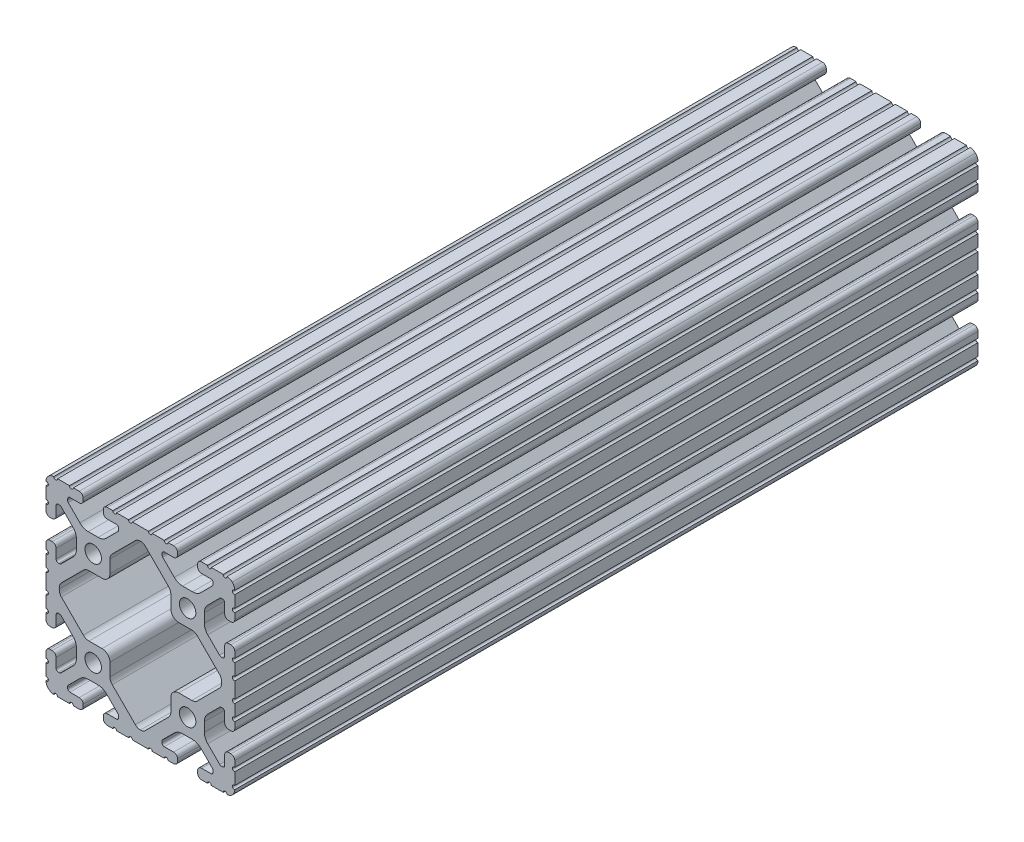
SolidWorks part; units mm, degrees
ref_plane "Front Plane" through (0, 0, 0) normal (0, 0, 1) x (1, 0, 0)
ref_plane "Top Plane" through (0, 0, 0) normal (0, 1, 0) x (1, 0, 0)
ref_plane "Right Plane" through (0, 0, 0) normal (1, 0, 0) x (0, 0, -1)
sketch "Sketch1" plane through (0, 0, 0) normal (0, 0, 1) x (1, 0, 0)
  line L0 (0, 38.1) -> (0, -38.1) construction
  line L1 (-38.1, -38.1) -> (38.1, -38.1) construction
  line L2 (-38.1, -38.1) -> (-38.1, 38.1) construction
  line L3 (-38.1, 38.1) -> (38.1, 38.1) construction
  line L4 (38.1, -38.1) -> (38.1, 38.1) construction
  line L5 (0, 38.1) -> (0, -38.1) construction
  line L6 (-38.1, 0) -> (38.1, 0) construction
  line L7 (-19.05, 19.05) -> (19.05, 19.05) construction
  line L8 (-19.05, 19.05) -> (-19.05, -19.05) construction
  line L9 (-19.05, -19.05) -> (19.05, -19.05) construction
  line L10 (19.05, 19.05) -> (19.05, -19.05) construction
  line L11 (-23.114, 38.1) -> (-23.114, -38.1) construction
  line L12 (-23.114, -38.1) -> (-14.986, 38.1) construction
  line L13 (-14.986, 38.1) -> (-14.986, -38.1) construction
  circle A0 centre (19.05, 19.05) radius 3.3274
  point P0 (0, 0)
  point P9 (0, 0)
  point P12 (-19.05, 0)
  line B0 (-11.3637, -22.8433) -> (-2.0515, -32.1555)
  line B1 (-12.2936, -15.4686) -> (-12.2936, -20.5983)
  line B2 (-20.769, -12.2936) -> (-15.4686, -12.2936)
  line B3 (-31.9021, -2.4756) -> (-23.0141, -11.3637)
  line B4 (-23.0141, 11.3637) -> (-31.9021, 2.4756)
  line B5 (-15.4686, 12.2936) -> (-20.769, 12.2936)
  line B6 (-12.2936, 20.5983) -> (-12.2936, 15.4686)
  line B7 (-2.0515, 32.1555) -> (-11.3637, 22.8433)
  line B8 (11.3637, 22.8433) -> (2.0515, 32.1555)
  line B9 (12.2936, 15.4686) -> (12.2936, 20.5983)
  line B10 (20.769, 12.2936) -> (15.4686, 12.2936)
  line B11 (31.9021, 2.4756) -> (23.0141, 11.3637)
  line B12 (23.0141, -11.3637) -> (31.9021, -2.4756)
  line B13 (15.4686, -12.2936) -> (20.769, -12.2936)
  line B14 (12.2936, -20.5983) -> (12.2936, -15.4686)
  line B15 (2.0515, -32.1555) -> (11.3637, -22.8433)
  line B16 (-4.7773, 38.1) -> (-9.6053, 38.1)
  line B17 (-11.1289, 38.1) -> (-13.4112, 38.1)
  line B18 (-14.986, 36.5252) -> (-14.986, 35.6108)
  line B19 (-13.4112, 34.036) -> (-9.652, 34.036)
  line B20 (-8.763, 33.147) -> (-8.763, 32.4935)
  line B21 (-9.0234, 31.8649) -> (-13.6907, 27.1976)
  line B22 (-17.0493, 25.8064) -> (-21.0507, 25.8064)
  line B23 (-24.4093, 27.1976) -> (-29.1002, 31.8885)
  line B24 (-29.337, 32.7207) -> (-29.337, 33.147)
  line B25 (-28.448, 34.036) -> (-24.6888, 34.036)
  line B26 (-23.114, 35.6108) -> (-23.114, 36.5252)
  line B27 (-24.6888, 38.1) -> (-27.0772, 38.1)
  line B28 (-28.6011, 38.1) -> (-33.4288, 38.1)
  line B29 (-38.1, 33.373) -> (-38.1, 28.5453)
  line B30 (-38.1, 27.0238) -> (-38.1, 24.6302)
  line B31 (-36.5252, 23.0554) -> (-35.6108, 23.0554)
  line B32 (-34.036, 24.6302) -> (-34.036, 28.448)
  line B33 (-33.147, 29.337) -> (-32.6643, 29.337)
  line B34 (-32.0357, 29.0766) -> (-27.1976, 24.2385)
  line B35 (-25.8064, 20.8799) -> (-25.8064, 17.2201)
  line B36 (-27.1976, 13.8615) -> (-31.9489, 9.1101)
  line B37 (-32.7869, 8.763) -> (-33.0603, 8.763)
  line B38 (-34.036, 9.7387) -> (-34.036, 13.4698)
  line B39 (-35.6108, 15.0446) -> (-36.5252, 15.0446)
  line B40 (-38.1, 13.4698) -> (-38.1, 11.075)
  line B41 (-38.1, 9.552) -> (-38.1, 4.7238)
  line B42 (-38.1, 3.2007) -> (-38.1, -3.2007)
  line B43 (-38.1, -4.7238) -> (-38.1, -9.552)
  line B44 (-38.1, -11.075) -> (-38.1, -13.4698)
  line B45 (-36.5252, -15.0446) -> (-35.6108, -15.0446)
  line B46 (-34.036, -13.4698) -> (-34.036, -9.7387)
  line B47 (-33.0603, -8.763) -> (-32.7869, -8.763)
  line B48 (-31.9489, -9.1101) -> (-27.1976, -13.8615)
  line B49 (-25.8064, -17.2201) -> (-25.8064, -20.8799)
  line B50 (-27.1976, -24.2385) -> (-32.0357, -29.0766)
  line B51 (-32.6643, -29.337) -> (-33.147, -29.337)
  line B52 (-34.036, -28.448) -> (-34.036, -24.6302)
  line B53 (-35.6108, -23.0554) -> (-36.5252, -23.0554)
  line B54 (-38.1, -24.6302) -> (-38.1, -27.0238)
  line B55 (-38.1, -28.5453) -> (-38.1, -33.373)
  line B56 (-33.4288, -38.1) -> (-28.6011, -38.1)
  line B57 (-27.0772, -38.1) -> (-24.6888, -38.1)
  line B58 (-23.114, -36.5252) -> (-23.114, -35.6108)
  line B59 (-24.6888, -34.036) -> (-28.448, -34.036)
  line B60 (-29.337, -33.147) -> (-29.337, -32.7207)
  line B61 (-29.1002, -31.8885) -> (-24.4093, -27.1976)
  line B62 (-21.0507, -25.8064) -> (-17.0493, -25.8064)
  line B63 (-13.6907, -27.1976) -> (-9.0234, -31.8649)
  line B64 (-8.763, -32.4935) -> (-8.763, -33.147)
  line B65 (-9.652, -34.036) -> (-13.4112, -34.036)
  line B66 (-14.986, -35.6108) -> (-14.986, -36.5252)
  line B67 (-13.4112, -38.1) -> (-11.1289, -38.1)
  line B68 (-9.6053, -38.1) -> (-4.7773, -38.1)
  line B69 (-3.2537, -38.1) -> (3.2537, -38.1)
  line B70 (4.7773, -38.1) -> (9.6053, -38.1)
  line B71 (11.1289, -38.1) -> (13.4112, -38.1)
  line B72 (14.986, -36.5252) -> (14.986, -35.6108)
  line B73 (13.4112, -34.036) -> (9.652, -34.036)
  line B74 (8.763, -33.147) -> (8.763, -32.4935)
  line B75 (9.0234, -31.8649) -> (13.6907, -27.1976)
  line B76 (17.0493, -25.8064) -> (21.0507, -25.8064)
  line B77 (24.4093, -27.1976) -> (29.1002, -31.8885)
  line B78 (29.337, -32.7207) -> (29.337, -33.147)
  line B79 (28.448, -34.036) -> (24.6888, -34.036)
  line B80 (23.114, -35.6108) -> (23.114, -36.5252)
  line B81 (24.6888, -38.1) -> (27.0772, -38.1)
  line B82 (28.6011, -38.1) -> (33.4288, -38.1)
  line B83 (38.1, -33.373) -> (38.1, -28.5453)
  line B84 (38.1, -27.0238) -> (38.1, -24.6302)
  line B85 (36.5252, -23.0554) -> (35.6108, -23.0554)
  line B86 (34.036, -24.6302) -> (34.036, -28.448)
  line B87 (33.147, -29.337) -> (32.6643, -29.337)
  line B88 (32.0357, -29.0766) -> (27.1976, -24.2385)
  line B89 (25.8064, -20.8799) -> (25.8064, -17.2201)
  line B90 (27.1976, -13.8615) -> (31.9489, -9.1101)
  line B91 (32.7869, -8.763) -> (33.0603, -8.763)
  line B92 (34.036, -9.7387) -> (34.036, -13.4698)
  line B93 (35.6108, -15.0446) -> (36.5252, -15.0446)
  line B94 (38.1, -13.4698) -> (38.1, -11.075)
  line B95 (38.1, -9.552) -> (38.1, -4.7238)
  line B96 (38.1, -3.2007) -> (38.1, 3.2007)
  line B97 (38.1, 4.7238) -> (38.1, 9.552)
  line B98 (38.1, 11.075) -> (38.1, 13.4698)
  line B99 (36.5252, 15.0446) -> (35.6108, 15.0446)
  line B100 (34.036, 13.4698) -> (34.036, 9.7387)
  line B101 (33.0603, 8.763) -> (32.7869, 8.763)
  line B102 (31.9489, 9.1101) -> (27.1976, 13.8615)
  line B103 (25.8064, 17.2201) -> (25.8064, 20.8799)
  line B104 (27.1976, 24.2385) -> (32.0357, 29.0766)
  line B105 (32.6643, 29.337) -> (33.147, 29.337)
  line B106 (34.036, 28.448) -> (34.036, 24.6302)
  line B107 (35.6108, 23.0554) -> (36.5252, 23.0554)
  line B108 (38.1, 24.6302) -> (38.1, 27.0238)
  line B109 (38.1, 28.5453) -> (38.1, 33.373)
  line B110 (33.4288, 38.1) -> (28.6011, 38.1)
  line B111 (27.0772, 38.1) -> (24.6888, 38.1)
  line B112 (23.114, 36.5252) -> (23.114, 35.6108)
  line B113 (24.6888, 34.036) -> (28.448, 34.036)
  line B114 (29.337, 33.147) -> (29.337, 32.7207)
  line B115 (29.1002, 31.8885) -> (24.4093, 27.1976)
  line B116 (21.0507, 25.8064) -> (17.0493, 25.8064)
  line B117 (13.6907, 27.1976) -> (9.0234, 31.8649)
  line B118 (8.763, 32.4935) -> (8.763, 33.147)
  line B119 (9.652, 34.036) -> (13.4112, 34.036)
  line B120 (14.986, 35.6108) -> (14.986, 36.5252)
  line B121 (13.4112, 38.1) -> (11.1289, 38.1)
  line B122 (9.6053, 38.1) -> (4.7773, 38.1)
  line B123 (3.2537, 38.1) -> (-3.2537, 38.1)
  circle B124 centre (-19.05, 19.05) radius 3.3274
  circle B125 centre (-19.05, -19.05) radius 3.3274
  circle B126 centre (19.05, -19.05) radius 3.3274
  circle B127 centre (19.05, 19.05) radius 3.3274
  arc B128 (0, -33.011) -> (2.0515, -32.1555) centre (-0.0139, -30.09) ccw
  arc B129 (-2.0515, -32.1555) -> (0, -33.011) centre (0.0139, -30.09) ccw
  arc B130 (-12.2936, -20.5983) -> (-11.3637, -22.8433) centre (-9.1186, -20.5983) ccw
  arc B131 (-12.2936, -15.4686) -> (-15.4686, -12.2936) centre (-15.4686, -15.4686) ccw
  arc B132 (-23.0141, -11.3637) -> (-20.769, -12.2936) centre (-20.769, -9.1186) ccw
  arc B133 (-32.7287, 0) -> (-31.9021, -2.4756) centre (-29.8367, -0.4102) ccw
  arc B134 (-31.9021, 2.4756) -> (-32.7287, 0) centre (-29.8367, 0.4102) ccw
  arc B135 (-20.769, 12.2936) -> (-23.0141, 11.3637) centre (-20.769, 9.1186) ccw
  arc B136 (-15.4686, 12.2936) -> (-12.2936, 15.4686) centre (-15.4686, 15.4686) ccw
  arc B137 (-11.3637, 22.8433) -> (-12.2936, 20.5983) centre (-9.1186, 20.5983) ccw
  arc B138 (0, 33.011) -> (-2.0515, 32.1555) centre (0.0139, 30.09) ccw
  arc B139 (2.0515, 32.1555) -> (0, 33.011) centre (-0.0139, 30.09) ccw
  arc B140 (12.2936, 20.5983) -> (11.3637, 22.8433) centre (9.1186, 20.5983) ccw
  arc B141 (12.2936, 15.4686) -> (15.4686, 12.2936) centre (15.4686, 15.4686) ccw
  arc B142 (23.0141, 11.3637) -> (20.769, 12.2936) centre (20.769, 9.1186) ccw
  arc B143 (32.7287, 0) -> (31.9021, 2.4756) centre (29.8367, 0.4102) ccw
  arc B144 (31.9021, -2.4756) -> (32.7287, 0) centre (29.8367, -0.4102) ccw
  arc B145 (20.769, -12.2936) -> (23.0141, -11.3637) centre (20.769, -9.1186) ccw
  arc B146 (15.4686, -12.2936) -> (12.2936, -15.4686) centre (15.4686, -15.4686) ccw
  arc B147 (11.3637, -22.8433) -> (12.2936, -20.5983) centre (9.1186, -20.5983) ccw
  arc B148 (-4.7773, 38.1) -> (-3.2537, 38.1) centre (-4.0155, 38.0824) ccw
  arc B149 (-11.1289, 38.1) -> (-9.6053, 38.1) centre (-10.3671, 38.0824) ccw
  arc B150 (-13.4112, 38.1) -> (-14.986, 36.5252) centre (-13.4112, 36.5252) ccw
  arc B151 (-14.986, 35.6108) -> (-13.4112, 34.036) centre (-13.4112, 35.6108) ccw
  arc B152 (-8.763, 33.147) -> (-9.652, 34.036) centre (-9.652, 33.147) ccw
  arc B153 (-9.0234, 31.8649) -> (-8.763, 32.4935) centre (-9.652, 32.4935) ccw
  arc B154 (-17.0493, 25.8064) -> (-13.6907, 27.1976) centre (-17.0493, 30.5562) ccw
  arc B155 (-24.4093, 27.1976) -> (-21.0507, 25.8064) centre (-21.0507, 30.5562) ccw
  arc B156 (-29.337, 32.7207) -> (-29.1002, 31.8885) centre (-28.4716, 32.5172) ccw
  arc B157 (-28.448, 34.036) -> (-29.337, 33.147) centre (-28.448, 33.147) ccw
  arc B158 (-24.6888, 34.036) -> (-23.114, 35.6108) centre (-24.6888, 35.6108) ccw
  arc B159 (-23.114, 36.5252) -> (-24.6888, 38.1) centre (-24.6888, 36.5252) ccw
  arc B160 (-28.6011, 38.1) -> (-27.0772, 38.1) centre (-27.8392, 38.0824) ccw
  arc B161 (-34.9527, 38.1) -> (-33.4288, 38.1) centre (-34.1907, 38.0824) ccw
  arc B162 (-34.9527, 38.1) -> (-37.0861, 37.1826) centre (-34.8521, 34.9266) ccw
  arc B163 (-37.0861, 37.1826) -> (-38.1, 34.8455) centre (-34.925, 34.8566) ccw
  arc B164 (-38.1, 33.373) -> (-38.1, 34.8455) centre (-37.9035, 34.1092) ccw
  arc B165 (-38.1, 27.0238) -> (-38.1, 28.5453) centre (-37.9035, 27.7845) ccw
  arc B166 (-38.1, 24.6302) -> (-36.5252, 23.0554) centre (-36.5252, 24.6302) ccw
  arc B167 (-35.6108, 23.0554) -> (-34.036, 24.6302) centre (-35.6108, 24.6302) ccw
  arc B168 (-33.147, 29.337) -> (-34.036, 28.448) centre (-33.147, 28.448) ccw
  arc B169 (-32.0357, 29.0766) -> (-32.6643, 29.337) centre (-32.6643, 28.448) ccw
  arc B170 (-25.8064, 20.8799) -> (-27.1976, 24.2385) centre (-30.5562, 20.8799) ccw
  arc B171 (-27.1976, 13.8615) -> (-25.8064, 17.2201) centre (-30.5562, 17.2201) ccw
  arc B172 (-32.7869, 8.763) -> (-31.9489, 9.1101) centre (-32.7869, 9.9481) ccw
  arc B173 (-34.036, 9.7387) -> (-33.0603, 8.763) centre (-33.0603, 9.7387) ccw
  arc B174 (-34.036, 13.4698) -> (-35.6108, 15.0446) centre (-35.6108, 13.4698) ccw
  arc B175 (-36.5252, 15.0446) -> (-38.1, 13.4698) centre (-36.5252, 13.4698) ccw
  arc B176 (-38.1, 9.552) -> (-38.1, 11.075) centre (-37.9035, 10.3135) ccw
  arc B177 (-38.1, 3.2007) -> (-38.1, 4.7238) centre (-37.9035, 3.9622) ccw
  arc B178 (-38.1, -4.7238) -> (-38.1, -3.2007) centre (-37.9035, -3.9622) ccw
  arc B179 (-38.1, -11.075) -> (-38.1, -9.552) centre (-37.9035, -10.3135) ccw
  arc B180 (-38.1, -13.4698) -> (-36.5252, -15.0446) centre (-36.5252, -13.4698) ccw
  arc B181 (-35.6108, -15.0446) -> (-34.036, -13.4698) centre (-35.6108, -13.4698) ccw
  arc B182 (-33.0603, -8.763) -> (-34.036, -9.7387) centre (-33.0603, -9.7387) ccw
  arc B183 (-31.9489, -9.1101) -> (-32.7869, -8.763) centre (-32.7869, -9.9481) ccw
  arc B184 (-25.8064, -17.2201) -> (-27.1976, -13.8615) centre (-30.5562, -17.2201) ccw
  arc B185 (-27.1976, -24.2385) -> (-25.8064, -20.8799) centre (-30.5562, -20.8799) ccw
  arc B186 (-32.6643, -29.337) -> (-32.0357, -29.0766) centre (-32.6643, -28.448) ccw
  arc B187 (-34.036, -28.448) -> (-33.147, -29.337) centre (-33.147, -28.448) ccw
  arc B188 (-34.036, -24.6302) -> (-35.6108, -23.0554) centre (-35.6108, -24.6302) ccw
  arc B189 (-36.5252, -23.0554) -> (-38.1, -24.6302) centre (-36.5252, -24.6302) ccw
  arc B190 (-38.1, -28.5453) -> (-38.1, -27.0238) centre (-37.9035, -27.7845) ccw
  arc B191 (-38.1, -34.8455) -> (-38.1, -33.373) centre (-37.9035, -34.1092) ccw
  arc B192 (-38.1, -34.8455) -> (-37.0861, -37.1826) centre (-34.925, -34.8566) ccw
  arc B193 (-37.0861, -37.1826) -> (-34.9527, -38.1) centre (-34.8521, -34.9266) ccw
  arc B194 (-33.4288, -38.1) -> (-34.9527, -38.1) centre (-34.1907, -38.0824) ccw
  arc B195 (-27.0772, -38.1) -> (-28.6011, -38.1) centre (-27.8392, -38.0824) ccw
  arc B196 (-24.6888, -38.1) -> (-23.114, -36.5252) centre (-24.6888, -36.5252) ccw
  arc B197 (-23.114, -35.6108) -> (-24.6888, -34.036) centre (-24.6888, -35.6108) ccw
  arc B198 (-29.337, -33.147) -> (-28.448, -34.036) centre (-28.448, -33.147) ccw
  arc B199 (-29.1002, -31.8885) -> (-29.337, -32.7207) centre (-28.4716, -32.5172) ccw
  arc B200 (-21.0507, -25.8064) -> (-24.4093, -27.1976) centre (-21.0507, -30.5562) ccw
  arc B201 (-13.6907, -27.1976) -> (-17.0493, -25.8064) centre (-17.0493, -30.5562) ccw
  arc B202 (-8.763, -32.4935) -> (-9.0234, -31.8649) centre (-9.652, -32.4935) ccw
  arc B203 (-9.652, -34.036) -> (-8.763, -33.147) centre (-9.652, -33.147) ccw
  arc B204 (-13.4112, -34.036) -> (-14.986, -35.6108) centre (-13.4112, -35.6108) ccw
  arc B205 (-14.986, -36.5252) -> (-13.4112, -38.1) centre (-13.4112, -36.5252) ccw
  arc B206 (-9.6053, -38.1) -> (-11.1289, -38.1) centre (-10.3671, -38.0824) ccw
  arc B207 (-3.2537, -38.1) -> (-4.7773, -38.1) centre (-4.0155, -38.0824) ccw
  arc B208 (4.7773, -38.1) -> (3.2537, -38.1) centre (4.0155, -38.0824) ccw
  arc B209 (11.1289, -38.1) -> (9.6053, -38.1) centre (10.3671, -38.0824) ccw
  arc B210 (13.4112, -38.1) -> (14.986, -36.5252) centre (13.4112, -36.5252) ccw
  arc B211 (14.986, -35.6108) -> (13.4112, -34.036) centre (13.4112, -35.6108) ccw
  arc B212 (8.763, -33.147) -> (9.652, -34.036) centre (9.652, -33.147) ccw
  arc B213 (9.0234, -31.8649) -> (8.763, -32.4935) centre (9.652, -32.4935) ccw
  arc B214 (17.0493, -25.8064) -> (13.6907, -27.1976) centre (17.0493, -30.5562) ccw
  arc B215 (24.4093, -27.1976) -> (21.0507, -25.8064) centre (21.0507, -30.5562) ccw
  arc B216 (29.337, -32.7207) -> (29.1002, -31.8885) centre (28.4716, -32.5172) ccw
  arc B217 (28.448, -34.036) -> (29.337, -33.147) centre (28.448, -33.147) ccw
  arc B218 (24.6888, -34.036) -> (23.114, -35.6108) centre (24.6888, -35.6108) ccw
  arc B219 (23.114, -36.5252) -> (24.6888, -38.1) centre (24.6888, -36.5252) ccw
  arc B220 (28.6011, -38.1) -> (27.0772, -38.1) centre (27.8392, -38.0824) ccw
  arc B221 (34.9527, -38.1) -> (33.4288, -38.1) centre (34.1907, -38.0824) ccw
  arc B222 (34.9527, -38.1) -> (37.0861, -37.1826) centre (34.8521, -34.9266) ccw
  arc B223 (37.0861, -37.1826) -> (38.1, -34.8455) centre (34.925, -34.8566) ccw
  arc B224 (38.1, -33.373) -> (38.1, -34.8455) centre (37.9035, -34.1092) ccw
  arc B225 (38.1, -27.0238) -> (38.1, -28.5453) centre (37.9035, -27.7845) ccw
  arc B226 (38.1, -24.6302) -> (36.5252, -23.0554) centre (36.5252, -24.6302) ccw
  arc B227 (35.6108, -23.0554) -> (34.036, -24.6302) centre (35.6108, -24.6302) ccw
  arc B228 (33.147, -29.337) -> (34.036, -28.448) centre (33.147, -28.448) ccw
  arc B229 (32.0357, -29.0766) -> (32.6643, -29.337) centre (32.6643, -28.448) ccw
  arc B230 (25.8064, -20.8799) -> (27.1976, -24.2385) centre (30.5562, -20.8799) ccw
  arc B231 (27.1976, -13.8615) -> (25.8064, -17.2201) centre (30.5562, -17.2201) ccw
  arc B232 (32.7869, -8.763) -> (31.9489, -9.1101) centre (32.7869, -9.9481) ccw
  arc B233 (34.036, -9.7387) -> (33.0603, -8.763) centre (33.0603, -9.7387) ccw
  arc B234 (34.036, -13.4698) -> (35.6108, -15.0446) centre (35.6108, -13.4698) ccw
  arc B235 (36.5252, -15.0446) -> (38.1, -13.4698) centre (36.5252, -13.4698) ccw
  arc B236 (38.1, -9.552) -> (38.1, -11.075) centre (37.9035, -10.3135) ccw
  arc B237 (38.1, -3.2007) -> (38.1, -4.7238) centre (37.9035, -3.9622) ccw
  arc B238 (38.1, 4.7238) -> (38.1, 3.2007) centre (37.9035, 3.9622) ccw
  arc B239 (38.1, 11.075) -> (38.1, 9.552) centre (37.9035, 10.3135) ccw
  arc B240 (38.1, 13.4698) -> (36.5252, 15.0446) centre (36.5252, 13.4698) ccw
  arc B241 (35.6108, 15.0446) -> (34.036, 13.4698) centre (35.6108, 13.4698) ccw
  arc B242 (33.0603, 8.763) -> (34.036, 9.7387) centre (33.0603, 9.7387) ccw
  arc B243 (31.9489, 9.1101) -> (32.7869, 8.763) centre (32.7869, 9.9481) ccw
  arc B244 (25.8064, 17.2201) -> (27.1976, 13.8615) centre (30.5562, 17.2201) ccw
  arc B245 (27.1976, 24.2385) -> (25.8064, 20.8799) centre (30.5562, 20.8799) ccw
  arc B246 (32.6643, 29.337) -> (32.0357, 29.0766) centre (32.6643, 28.448) ccw
  arc B247 (34.036, 28.448) -> (33.147, 29.337) centre (33.147, 28.448) ccw
  arc B248 (34.036, 24.6302) -> (35.6108, 23.0554) centre (35.6108, 24.6302) ccw
  arc B249 (36.5252, 23.0554) -> (38.1, 24.6302) centre (36.5252, 24.6302) ccw
  arc B250 (38.1, 28.5453) -> (38.1, 27.0238) centre (37.9035, 27.7845) ccw
  arc B251 (38.1, 34.8455) -> (38.1, 33.373) centre (37.9035, 34.1092) ccw
  arc B252 (38.1, 34.8455) -> (37.0861, 37.1826) centre (34.925, 34.8566) ccw
  arc B253 (37.0861, 37.1826) -> (34.9527, 38.1) centre (34.8521, 34.9266) ccw
  arc B254 (33.4288, 38.1) -> (34.9527, 38.1) centre (34.1907, 38.0824) ccw
  arc B255 (27.0772, 38.1) -> (28.6011, 38.1) centre (27.8392, 38.0824) ccw
  arc B256 (24.6888, 38.1) -> (23.114, 36.5252) centre (24.6888, 36.5252) ccw
  arc B257 (23.114, 35.6108) -> (24.6888, 34.036) centre (24.6888, 35.6108) ccw
  arc B258 (29.337, 33.147) -> (28.448, 34.036) centre (28.448, 33.147) ccw
  arc B259 (29.1002, 31.8885) -> (29.337, 32.7207) centre (28.4716, 32.5172) ccw
  arc B260 (21.0507, 25.8064) -> (24.4093, 27.1976) centre (21.0507, 30.5562) ccw
  arc B261 (13.6907, 27.1976) -> (17.0493, 25.8064) centre (17.0493, 30.5562) ccw
  arc B262 (8.763, 32.4935) -> (9.0234, 31.8649) centre (9.652, 32.4935) ccw
  arc B263 (9.652, 34.036) -> (8.763, 33.147) centre (9.652, 33.147) ccw
  arc B264 (13.4112, 34.036) -> (14.986, 35.6108) centre (13.4112, 35.6108) ccw
  arc B265 (14.986, 36.5252) -> (13.4112, 38.1) centre (13.4112, 36.5252) ccw
  arc B266 (9.6053, 38.1) -> (11.1289, 38.1) centre (10.3671, 38.0824) ccw
  arc B267 (3.2537, 38.1) -> (4.7773, 38.1) centre (4.0155, 38.0824) ccw
  dimension "Center Hole Diameter" = 6.6548
  dimension "Rail Width" = 76.2
  dimension "Rail Height" = 76.2
  dimension "T-Slot Width" = 8.128
sketch_block_instance "Block1-1"
sketch_block "Block1"
sketch "Sketch2" plane through (0, 0, 0) normal (1, 0, 0) x (0, 0, -1)
  line L0 (-150, 0) -> (150, 0) construction
  line L1 (-150, 38.1) -> (-150, -38.1) construction
  line L2 (-150, -38.1) -> (150, -38.1) construction
  line L3 (150, -38.1) -> (150, 38.1) construction
  line L4 (-48.4, 0) -> (-48.4, 38.1) construction
  line L5 (-48.4, 38.1) -> (48.4, 38.1) construction
  line L6 (48.4, 38.1) -> (48.4, 0) construction
  point P5 (48.4, 0)
  point P10 (-48.4, 0)
  dimension "D1" = 101.6
  dimension "Length" = 300
  dimension "D2" = 101.6
sketch "Sketch3" plane through (0, 0, 0) normal (0, 0, 1) x (1, 0, 0)
  line L0 (-11.3637, -22.8433) -> (-2.0515, -32.1555) construction
  line L1 (-12.2936, -15.4686) -> (-12.2936, -20.5983) construction
  line L2 (-20.769, -12.2936) -> (-15.4686, -12.2936) construction
  line L3 (-31.9021, -2.4756) -> (-23.0141, -11.3637) construction
  line L4 (-23.0141, 11.3637) -> (-31.9021, 2.4756) construction
  line L5 (-15.4686, 12.2936) -> (-20.769, 12.2936) construction
  line L6 (-12.2936, 20.5983) -> (-12.2936, 15.4686) construction
  line L7 (-2.0515, 32.1555) -> (-11.3637, 22.8433) construction
  line L8 (11.3637, 22.8433) -> (2.0515, 32.1555) construction
  line L9 (12.2936, 15.4686) -> (12.2936, 20.5983) construction
  line L10 (20.769, 12.2936) -> (15.4686, 12.2936) construction
  line L11 (31.9021, 2.4756) -> (23.0141, 11.3637) construction
  line L12 (23.0141, -11.3637) -> (31.9021, -2.4756) construction
  line L13 (15.4686, -12.2936) -> (20.769, -12.2936) construction
  line L14 (12.2936, -20.5983) -> (12.2936, -15.4686) construction
  line L15 (2.0515, -32.1555) -> (11.3637, -22.8433) construction
  line L16 (34.036, 28.448) -> (34.036, 24.6302) construction
  line L17 (35.6108, 23.0554) -> (36.5252, 23.0554) construction
  line L18 (38.1, 24.6302) -> (38.1, 27.0238) construction
  line L19 (38.1, 28.5453) -> (38.1, 33.373) construction
  line L20 (33.4288, 38.1) -> (28.6011, 38.1) construction
  line L21 (27.0772, 38.1) -> (24.6888, 38.1) construction
  line L22 (23.114, 36.5252) -> (23.114, 35.6108) construction
  line L23 (24.6888, 34.036) -> (28.448, 34.036) construction
  line L24 (29.337, 33.147) -> (29.337, 32.7207) construction
  line L25 (29.1002, 31.8885) -> (24.4093, 27.1976) construction
  line L26 (21.0507, 25.8064) -> (17.0493, 25.8064) construction
  line L27 (13.6907, 27.1976) -> (9.0234, 31.8649) construction
  line L28 (8.763, 32.4935) -> (8.763, 33.147) construction
  line L29 (9.652, 34.036) -> (13.4112, 34.036) construction
  line L30 (14.986, 35.6108) -> (14.986, 36.5252) construction
  line L31 (13.4112, 38.1) -> (11.1289, 38.1) construction
  line L32 (9.6053, 38.1) -> (4.7773, 38.1) construction
  line L33 (3.2537, 38.1) -> (-3.2537, 38.1) construction
  line L34 (-4.7773, 38.1) -> (-9.6053, 38.1) construction
  line L35 (-11.1289, 38.1) -> (-13.4112, 38.1) construction
  line L36 (-14.986, 36.5252) -> (-14.986, 35.6108) construction
  line L37 (-13.4112, 34.036) -> (-9.652, 34.036) construction
  line L38 (-8.763, 33.147) -> (-8.763, 32.4935) construction
  line L39 (-9.0234, 31.8649) -> (-13.6907, 27.1976) construction
  line L40 (-17.0493, 25.8064) -> (-21.0507, 25.8064) construction
  line L41 (-24.4093, 27.1976) -> (-29.1002, 31.8885) construction
  line L42 (-29.337, 32.7207) -> (-29.337, 33.147) construction
  line L43 (-28.448, 34.036) -> (-24.6888, 34.036) construction
  line L44 (-23.114, 35.6108) -> (-23.114, 36.5252) construction
  line L45 (-24.6888, 38.1) -> (-27.0772, 38.1) construction
  line L46 (-28.6011, 38.1) -> (-33.4288, 38.1) construction
  line L47 (-38.1, 33.373) -> (-38.1, 28.5453) construction
  line L48 (-38.1, 27.0238) -> (-38.1, 24.6302) construction
  line L49 (-36.5252, 23.0554) -> (-35.6108, 23.0554) construction
  line L50 (-34.036, 24.6302) -> (-34.036, 28.448) construction
  line L51 (-33.147, 29.337) -> (-32.6643, 29.337) construction
  line L52 (-32.0357, 29.0766) -> (-27.1976, 24.2385) construction
  line L53 (-25.8064, 20.8799) -> (-25.8064, 17.2201) construction
  line L54 (-27.1976, 13.8615) -> (-31.9489, 9.1101) construction
  line L55 (-32.7869, 8.763) -> (-33.0603, 8.763) construction
  line L56 (-34.036, 9.7387) -> (-34.036, 13.4698) construction
  line L57 (-35.6108, 15.0446) -> (-36.5252, 15.0446) construction
  line L58 (-38.1, 13.4698) -> (-38.1, 11.075) construction
  line L59 (-38.1, 9.552) -> (-38.1, 4.7238) construction
  line L60 (-38.1, 3.2007) -> (-38.1, -3.2007) construction
  line L61 (-38.1, -4.7238) -> (-38.1, -9.552) construction
  line L62 (-38.1, -11.075) -> (-38.1, -13.4698) construction
  line L63 (-36.5252, -15.0446) -> (-35.6108, -15.0446) construction
  line L64 (-34.036, -13.4698) -> (-34.036, -9.7387) construction
  line L65 (-33.0603, -8.763) -> (-32.7869, -8.763) construction
  line L66 (-31.9489, -9.1101) -> (-27.1976, -13.8615) construction
  line L67 (-25.8064, -17.2201) -> (-25.8064, -20.8799) construction
  line L68 (-27.1976, -24.2385) -> (-32.0357, -29.0766) construction
  line L69 (-32.6643, -29.337) -> (-33.147, -29.337) construction
  line L70 (-34.036, -28.448) -> (-34.036, -24.6302) construction
  line L71 (-35.6108, -23.0554) -> (-36.5252, -23.0554) construction
  line L72 (-38.1, -24.6302) -> (-38.1, -27.0238) construction
  line L73 (-38.1, -28.5453) -> (-38.1, -33.373) construction
  line L74 (-33.4288, -38.1) -> (-28.6011, -38.1) construction
  line L75 (-27.0772, -38.1) -> (-24.6888, -38.1) construction
  line L76 (-23.114, -36.5252) -> (-23.114, -35.6108) construction
  line L77 (-24.6888, -34.036) -> (-28.448, -34.036) construction
  line L78 (-29.337, -33.147) -> (-29.337, -32.7207) construction
  line L79 (-29.1002, -31.8885) -> (-24.4093, -27.1976) construction
  line L80 (-21.0507, -25.8064) -> (-17.0493, -25.8064) construction
  line L81 (-13.6907, -27.1976) -> (-9.0234, -31.8649) construction
  line L82 (-8.763, -32.4935) -> (-8.763, -33.147) construction
  line L83 (-9.652, -34.036) -> (-13.4112, -34.036) construction
  line L84 (-14.986, -35.6108) -> (-14.986, -36.5252) construction
  line L85 (-13.4112, -38.1) -> (-11.1289, -38.1) construction
  line L86 (-9.6053, -38.1) -> (-4.7773, -38.1) construction
  line L87 (-3.2537, -38.1) -> (3.2537, -38.1) construction
  line L88 (4.7773, -38.1) -> (9.6053, -38.1) construction
  line L89 (11.1289, -38.1) -> (13.4112, -38.1) construction
  line L90 (14.986, -36.5252) -> (14.986, -35.6108) construction
  line L91 (13.4112, -34.036) -> (9.652, -34.036) construction
  line L92 (8.763, -33.147) -> (8.763, -32.4935) construction
  line L93 (9.0234, -31.8649) -> (13.6907, -27.1976) construction
  line L94 (17.0493, -25.8064) -> (21.0507, -25.8064) construction
  line L95 (24.4093, -27.1976) -> (29.1002, -31.8885) construction
  line L96 (29.337, -32.7207) -> (29.337, -33.147) construction
  line L97 (28.448, -34.036) -> (24.6888, -34.036) construction
  line L98 (23.114, -35.6108) -> (23.114, -36.5252) construction
  line L99 (24.6888, -38.1) -> (27.0772, -38.1) construction
  line L100 (28.6011, -38.1) -> (33.4288, -38.1) construction
  line L101 (38.1, -33.373) -> (38.1, -28.5453) construction
  line L102 (38.1, -27.0238) -> (38.1, -24.6302) construction
  line L103 (36.5252, -23.0554) -> (35.6108, -23.0554) construction
  line L104 (34.036, -24.6302) -> (34.036, -28.448) construction
  line L105 (33.147, -29.337) -> (32.6643, -29.337) construction
  line L106 (32.0357, -29.0766) -> (27.1976, -24.2385) construction
  line L107 (25.8064, -20.8799) -> (25.8064, -17.2201) construction
  line L108 (27.1976, -13.8615) -> (31.9489, -9.1101) construction
  line L109 (32.7869, -8.763) -> (33.0603, -8.763) construction
  line L110 (34.036, -9.7387) -> (34.036, -13.4698) construction
  line L111 (35.6108, -15.0446) -> (36.5252, -15.0446) construction
  line L112 (38.1, -13.4698) -> (38.1, -11.075) construction
  line L113 (38.1, -9.552) -> (38.1, -4.7238) construction
  line L114 (38.1, -3.2007) -> (38.1, 3.2007) construction
  line L115 (38.1, 4.7238) -> (38.1, 9.552) construction
  line L116 (38.1, 11.075) -> (38.1, 13.4698) construction
  line L117 (36.5252, 15.0446) -> (35.6108, 15.0446) construction
  line L118 (34.036, 13.4698) -> (34.036, 9.7387) construction
  line L119 (33.0603, 8.763) -> (32.7869, 8.763) construction
  line L120 (31.9489, 9.1101) -> (27.1976, 13.8615) construction
  line L121 (25.8064, 17.2201) -> (25.8064, 20.8799) construction
  line L122 (27.1976, 24.2385) -> (32.0357, 29.0766) construction
  line L123 (32.6643, 29.337) -> (33.147, 29.337) construction
  line L124 (-11.3637, -22.8433) -> (-2.0515, -32.1555)
  line L125 (-12.2936, -15.4686) -> (-12.2936, -20.5983)
  line L126 (-20.769, -12.2936) -> (-15.4686, -12.2936)
  line L127 (-31.9021, -2.4756) -> (-23.0141, -11.3637)
  line L128 (-23.0141, 11.3637) -> (-31.9021, 2.4756)
  line L129 (-15.4686, 12.2936) -> (-20.769, 12.2936)
  line L130 (-12.2936, 20.5983) -> (-12.2936, 15.4686)
  line L131 (-2.0515, 32.1555) -> (-11.3637, 22.8433)
  line L132 (11.3637, 22.8433) -> (2.0515, 32.1555)
  line L133 (12.2936, 15.4686) -> (12.2936, 20.5983)
  line L134 (20.769, 12.2936) -> (15.4686, 12.2936)
  line L135 (31.9021, 2.4756) -> (23.0141, 11.3637)
  line L136 (23.0141, -11.3637) -> (31.9021, -2.4756)
  line L137 (15.4686, -12.2936) -> (20.769, -12.2936)
  line L138 (12.2936, -20.5983) -> (12.2936, -15.4686)
  line L139 (2.0515, -32.1555) -> (11.3637, -22.8433)
  line L140 (34.036, 28.448) -> (34.036, 24.6302)
  line L141 (35.6108, 23.0554) -> (36.5252, 23.0554)
  line L142 (38.1, 24.6302) -> (38.1, 27.0238)
  line L143 (38.1, 28.5453) -> (38.1, 33.373)
  line L144 (33.4288, 38.1) -> (28.6011, 38.1)
  line L145 (27.0772, 38.1) -> (24.6888, 38.1)
  line L146 (23.114, 36.5252) -> (23.114, 35.6108)
  line L147 (24.6888, 34.036) -> (28.448, 34.036)
  line L148 (29.337, 33.147) -> (29.337, 32.7207)
  line L149 (29.1002, 31.8885) -> (24.4093, 27.1976)
  line L150 (21.0507, 25.8064) -> (17.0493, 25.8064)
  line L151 (13.6907, 27.1976) -> (9.0234, 31.8649)
  line L152 (8.763, 32.4935) -> (8.763, 33.147)
  line L153 (9.652, 34.036) -> (13.4112, 34.036)
  line L154 (14.986, 35.6108) -> (14.986, 36.5252)
  line L155 (13.4112, 38.1) -> (11.1289, 38.1)
  line L156 (9.6053, 38.1) -> (4.7773, 38.1)
  line L157 (3.2537, 38.1) -> (-3.2537, 38.1)
  line L158 (-4.7773, 38.1) -> (-9.6053, 38.1)
  line L159 (-11.1289, 38.1) -> (-13.4112, 38.1)
  line L160 (-14.986, 36.5252) -> (-14.986, 35.6108)
  line L161 (-13.4112, 34.036) -> (-9.652, 34.036)
  line L162 (-8.763, 33.147) -> (-8.763, 32.4935)
  line L163 (-9.0234, 31.8649) -> (-13.6907, 27.1976)
  line L164 (-17.0493, 25.8064) -> (-21.0507, 25.8064)
  line L165 (-24.4093, 27.1976) -> (-29.1002, 31.8885)
  line L166 (-29.337, 32.7207) -> (-29.337, 33.147)
  line L167 (-28.448, 34.036) -> (-24.6888, 34.036)
  line L168 (-23.114, 35.6108) -> (-23.114, 36.5252)
  line L169 (-24.6888, 38.1) -> (-27.0772, 38.1)
  line L170 (-28.6011, 38.1) -> (-33.4288, 38.1)
  line L171 (-38.1, 33.373) -> (-38.1, 28.5453)
  line L172 (-38.1, 27.0238) -> (-38.1, 24.6302)
  line L173 (-36.5252, 23.0554) -> (-35.6108, 23.0554)
  line L174 (-34.036, 24.6302) -> (-34.036, 28.448)
  line L175 (-33.147, 29.337) -> (-32.6643, 29.337)
  line L176 (-32.0357, 29.0766) -> (-27.1976, 24.2385)
  line L177 (-25.8064, 20.8799) -> (-25.8064, 17.2201)
  line L178 (-27.1976, 13.8615) -> (-31.9489, 9.1101)
  line L179 (-32.7869, 8.763) -> (-33.0603, 8.763)
  line L180 (-34.036, 9.7387) -> (-34.036, 13.4698)
  line L181 (-35.6108, 15.0446) -> (-36.5252, 15.0446)
  line L182 (-38.1, 13.4698) -> (-38.1, 11.075)
  line L183 (-38.1, 9.552) -> (-38.1, 4.7238)
  line L184 (-38.1, 3.2007) -> (-38.1, -3.2007)
  line L185 (-38.1, -4.7238) -> (-38.1, -9.552)
  line L186 (-38.1, -11.075) -> (-38.1, -13.4698)
  line L187 (-36.5252, -15.0446) -> (-35.6108, -15.0446)
  line L188 (-34.036, -13.4698) -> (-34.036, -9.7387)
  line L189 (-33.0603, -8.763) -> (-32.7869, -8.763)
  line L190 (-31.9489, -9.1101) -> (-27.1976, -13.8615)
  line L191 (-25.8064, -17.2201) -> (-25.8064, -20.8799)
  line L192 (-27.1976, -24.2385) -> (-32.0357, -29.0766)
  line L193 (-32.6643, -29.337) -> (-33.147, -29.337)
  line L194 (-34.036, -28.448) -> (-34.036, -24.6302)
  line L195 (-35.6108, -23.0554) -> (-36.5252, -23.0554)
  line L196 (-38.1, -24.6302) -> (-38.1, -27.0238)
  line L197 (-38.1, -28.5453) -> (-38.1, -33.373)
  line L198 (-33.4288, -38.1) -> (-28.6011, -38.1)
  line L199 (-27.0772, -38.1) -> (-24.6888, -38.1)
  line L200 (-23.114, -36.5252) -> (-23.114, -35.6108)
  line L201 (-24.6888, -34.036) -> (-28.448, -34.036)
  line L202 (-29.337, -33.147) -> (-29.337, -32.7207)
  line L203 (-29.1002, -31.8885) -> (-24.4093, -27.1976)
  line L204 (-21.0507, -25.8064) -> (-17.0493, -25.8064)
  line L205 (-13.6907, -27.1976) -> (-9.0234, -31.8649)
  line L206 (-8.763, -32.4935) -> (-8.763, -33.147)
  line L207 (-9.652, -34.036) -> (-13.4112, -34.036)
  line L208 (-14.986, -35.6108) -> (-14.986, -36.5252)
  line L209 (-13.4112, -38.1) -> (-11.1289, -38.1)
  line L210 (-9.6053, -38.1) -> (-4.7773, -38.1)
  line L211 (-3.2537, -38.1) -> (3.2537, -38.1)
  line L212 (4.7773, -38.1) -> (9.6053, -38.1)
  line L213 (11.1289, -38.1) -> (13.4112, -38.1)
  line L214 (14.986, -36.5252) -> (14.986, -35.6108)
  line L215 (13.4112, -34.036) -> (9.652, -34.036)
  line L216 (8.763, -33.147) -> (8.763, -32.4935)
  line L217 (9.0234, -31.8649) -> (13.6907, -27.1976)
  line L218 (17.0493, -25.8064) -> (21.0507, -25.8064)
  line L219 (24.4093, -27.1976) -> (29.1002, -31.8885)
  line L220 (29.337, -32.7207) -> (29.337, -33.147)
  line L221 (28.448, -34.036) -> (24.6888, -34.036)
  line L222 (23.114, -35.6108) -> (23.114, -36.5252)
  line L223 (24.6888, -38.1) -> (27.0772, -38.1)
  line L224 (28.6011, -38.1) -> (33.4288, -38.1)
  line L225 (38.1, -33.373) -> (38.1, -28.5453)
  line L226 (38.1, -27.0238) -> (38.1, -24.6302)
  line L227 (36.5252, -23.0554) -> (35.6108, -23.0554)
  line L228 (34.036, -24.6302) -> (34.036, -28.448)
  line L229 (33.147, -29.337) -> (32.6643, -29.337)
  line L230 (32.0357, -29.0766) -> (27.1976, -24.2385)
  line L231 (25.8064, -20.8799) -> (25.8064, -17.2201)
  line L232 (27.1976, -13.8615) -> (31.9489, -9.1101)
  line L233 (32.7869, -8.763) -> (33.0603, -8.763)
  line L234 (34.036, -9.7387) -> (34.036, -13.4698)
  line L235 (35.6108, -15.0446) -> (36.5252, -15.0446)
  line L236 (38.1, -13.4698) -> (38.1, -11.075)
  line L237 (38.1, -9.552) -> (38.1, -4.7238)
  line L238 (38.1, -3.2007) -> (38.1, 3.2007)
  line L239 (38.1, 4.7238) -> (38.1, 9.552)
  line L240 (38.1, 11.075) -> (38.1, 13.4698)
  line L241 (36.5252, 15.0446) -> (35.6108, 15.0446)
  line L242 (34.036, 13.4698) -> (34.036, 9.7387)
  line L243 (33.0603, 8.763) -> (32.7869, 8.763)
  line L244 (31.9489, 9.1101) -> (27.1976, 13.8615)
  line L245 (25.8064, 17.2201) -> (25.8064, 20.8799)
  line L246 (27.1976, 24.2385) -> (32.0357, 29.0766)
  line L247 (32.6643, 29.337) -> (33.147, 29.337)
  arc A0 (-2.0515, -32.1555) -> (0, -33.011) centre (0.0139, -30.09) ccw construction
  circle A1 centre (19.05, 19.05) radius 3.3274
  circle A2 centre (19.05, 19.05) radius 3.3274
  arc A3 (-12.2936, -20.5983) -> (-11.3637, -22.8433) centre (-9.1186, -20.5983) ccw construction
  arc A4 (-12.2936, -15.4686) -> (-15.4686, -12.2936) centre (-15.4686, -15.4686) ccw construction
  arc A5 (-23.0141, -11.3637) -> (-20.769, -12.2936) centre (-20.769, -9.1186) ccw construction
  arc A6 (-32.7287, 0) -> (-31.9021, -2.4756) centre (-29.8367, -0.4102) ccw construction
  arc A7 (-31.9021, 2.4756) -> (-32.7287, 0) centre (-29.8367, 0.4102) ccw construction
  arc A8 (-20.769, 12.2936) -> (-23.0141, 11.3637) centre (-20.769, 9.1186) ccw construction
  arc A9 (-15.4686, 12.2936) -> (-12.2936, 15.4686) centre (-15.4686, 15.4686) ccw construction
  arc A10 (-11.3637, 22.8433) -> (-12.2936, 20.5983) centre (-9.1186, 20.5983) ccw construction
  arc A11 (0, 33.011) -> (-2.0515, 32.1555) centre (0.0139, 30.09) ccw construction
  arc A12 (2.0515, 32.1555) -> (0, 33.011) centre (-0.0139, 30.09) ccw construction
  arc A13 (12.2936, 20.5983) -> (11.3637, 22.8433) centre (9.1186, 20.5983) ccw construction
  arc A14 (12.2936, 15.4686) -> (15.4686, 12.2936) centre (15.4686, 15.4686) ccw construction
  arc A15 (23.0141, 11.3637) -> (20.769, 12.2936) centre (20.769, 9.1186) ccw construction
  arc A16 (32.7287, 0) -> (31.9021, 2.4756) centre (29.8367, 0.4102) ccw construction
  arc A17 (31.9021, -2.4756) -> (32.7287, 0) centre (29.8367, -0.4102) ccw construction
  arc A18 (20.769, -12.2936) -> (23.0141, -11.3637) centre (20.769, -9.1186) ccw construction
  arc A19 (15.4686, -12.2936) -> (12.2936, -15.4686) centre (15.4686, -15.4686) ccw construction
  arc A20 (11.3637, -22.8433) -> (12.2936, -20.5983) centre (9.1186, -20.5983) ccw construction
  arc A21 (0, -33.011) -> (2.0515, -32.1555) centre (-0.0139, -30.09) ccw construction
  circle A22 centre (-19.05, 19.05) radius 3.3274 construction
  circle A23 centre (19.05, -19.05) radius 3.3274 construction
  circle A24 centre (-19.05, -19.05) radius 3.3274 construction
  circle A25 centre (19.05, 19.05) radius 3.3274 construction
  arc A26 (34.036, 24.6302) -> (35.6108, 23.0554) centre (35.6108, 24.6302) ccw construction
  arc A27 (36.5252, 23.0554) -> (38.1, 24.6302) centre (36.5252, 24.6302) ccw construction
  arc A28 (38.1, 28.5453) -> (38.1, 27.0238) centre (37.9035, 27.7845) ccw construction
  arc A29 (38.1, 34.8455) -> (38.1, 33.373) centre (37.9035, 34.1092) ccw construction
  arc A30 (38.1, 34.8455) -> (37.0861, 37.1826) centre (34.925, 34.8566) ccw construction
  arc A31 (37.0861, 37.1826) -> (34.9527, 38.1) centre (34.8521, 34.9266) ccw construction
  arc A32 (33.4288, 38.1) -> (34.9527, 38.1) centre (34.1907, 38.0824) ccw construction
  arc A33 (27.0772, 38.1) -> (28.6011, 38.1) centre (27.8392, 38.0824) ccw construction
  arc A34 (24.6888, 38.1) -> (23.114, 36.5252) centre (24.6888, 36.5252) ccw construction
  arc A35 (23.114, 35.6108) -> (24.6888, 34.036) centre (24.6888, 35.6108) ccw construction
  arc A36 (29.337, 33.147) -> (28.448, 34.036) centre (28.448, 33.147) ccw construction
  arc A37 (29.1002, 31.8885) -> (29.337, 32.7207) centre (28.4716, 32.5172) ccw construction
  arc A38 (21.0507, 25.8064) -> (24.4093, 27.1976) centre (21.0507, 30.5562) ccw construction
  arc A39 (13.6907, 27.1976) -> (17.0493, 25.8064) centre (17.0493, 30.5562) ccw construction
  arc A40 (8.763, 32.4935) -> (9.0234, 31.8649) centre (9.652, 32.4935) ccw construction
  arc A41 (9.652, 34.036) -> (8.763, 33.147) centre (9.652, 33.147) ccw construction
  arc A42 (13.4112, 34.036) -> (14.986, 35.6108) centre (13.4112, 35.6108) ccw construction
  arc A43 (14.986, 36.5252) -> (13.4112, 38.1) centre (13.4112, 36.5252) ccw construction
  arc A44 (9.6053, 38.1) -> (11.1289, 38.1) centre (10.3671, 38.0824) ccw construction
  arc A45 (3.2537, 38.1) -> (4.7773, 38.1) centre (4.0155, 38.0824) ccw construction
  arc A46 (-4.7773, 38.1) -> (-3.2537, 38.1) centre (-4.0155, 38.0824) ccw construction
  arc A47 (-11.1289, 38.1) -> (-9.6053, 38.1) centre (-10.3671, 38.0824) ccw construction
  arc A48 (-13.4112, 38.1) -> (-14.986, 36.5252) centre (-13.4112, 36.5252) ccw construction
  arc A49 (-14.986, 35.6108) -> (-13.4112, 34.036) centre (-13.4112, 35.6108) ccw construction
  arc A50 (-8.763, 33.147) -> (-9.652, 34.036) centre (-9.652, 33.147) ccw construction
  arc A51 (-9.0234, 31.8649) -> (-8.763, 32.4935) centre (-9.652, 32.4935) ccw construction
  arc A52 (-17.0493, 25.8064) -> (-13.6907, 27.1976) centre (-17.0493, 30.5562) ccw construction
  arc A53 (-24.4093, 27.1976) -> (-21.0507, 25.8064) centre (-21.0507, 30.5562) ccw construction
  arc A54 (-29.337, 32.7207) -> (-29.1002, 31.8885) centre (-28.4716, 32.5172) ccw construction
  arc A55 (-28.448, 34.036) -> (-29.337, 33.147) centre (-28.448, 33.147) ccw construction
  arc A56 (-24.6888, 34.036) -> (-23.114, 35.6108) centre (-24.6888, 35.6108) ccw construction
  arc A57 (-23.114, 36.5252) -> (-24.6888, 38.1) centre (-24.6888, 36.5252) ccw construction
  arc A58 (-28.6011, 38.1) -> (-27.0772, 38.1) centre (-27.8392, 38.0824) ccw construction
  arc A59 (-34.9527, 38.1) -> (-33.4288, 38.1) centre (-34.1907, 38.0824) ccw construction
  arc A60 (-34.9527, 38.1) -> (-37.0861, 37.1826) centre (-34.8521, 34.9266) ccw construction
  arc A61 (-37.0861, 37.1826) -> (-38.1, 34.8455) centre (-34.925, 34.8566) ccw construction
  arc A62 (-38.1, 33.373) -> (-38.1, 34.8455) centre (-37.9035, 34.1092) ccw construction
  arc A63 (-38.1, 27.0238) -> (-38.1, 28.5453) centre (-37.9035, 27.7845) ccw construction
  arc A64 (-38.1, 24.6302) -> (-36.5252, 23.0554) centre (-36.5252, 24.6302) ccw construction
  arc A65 (-35.6108, 23.0554) -> (-34.036, 24.6302) centre (-35.6108, 24.6302) ccw construction
  arc A66 (-33.147, 29.337) -> (-34.036, 28.448) centre (-33.147, 28.448) ccw construction
  arc A67 (-32.0357, 29.0766) -> (-32.6643, 29.337) centre (-32.6643, 28.448) ccw construction
  arc A68 (-25.8064, 20.8799) -> (-27.1976, 24.2385) centre (-30.5562, 20.8799) ccw construction
  arc A69 (-27.1976, 13.8615) -> (-25.8064, 17.2201) centre (-30.5562, 17.2201) ccw construction
  arc A70 (-32.7869, 8.763) -> (-31.9489, 9.1101) centre (-32.7869, 9.9481) ccw construction
  arc A71 (-34.036, 9.7387) -> (-33.0603, 8.763) centre (-33.0603, 9.7387) ccw construction
  arc A72 (-34.036, 13.4698) -> (-35.6108, 15.0446) centre (-35.6108, 13.4698) ccw construction
  arc A73 (-36.5252, 15.0446) -> (-38.1, 13.4698) centre (-36.5252, 13.4698) ccw construction
  arc A74 (-38.1, 9.552) -> (-38.1, 11.075) centre (-37.9035, 10.3135) ccw construction
  arc A75 (-38.1, 3.2007) -> (-38.1, 4.7238) centre (-37.9035, 3.9622) ccw construction
  arc A76 (-38.1, -4.7238) -> (-38.1, -3.2007) centre (-37.9035, -3.9622) ccw construction
  arc A77 (-38.1, -11.075) -> (-38.1, -9.552) centre (-37.9035, -10.3135) ccw construction
  arc A78 (-38.1, -13.4698) -> (-36.5252, -15.0446) centre (-36.5252, -13.4698) ccw construction
  arc A79 (-35.6108, -15.0446) -> (-34.036, -13.4698) centre (-35.6108, -13.4698) ccw construction
  arc A80 (-33.0603, -8.763) -> (-34.036, -9.7387) centre (-33.0603, -9.7387) ccw construction
  arc A81 (-31.9489, -9.1101) -> (-32.7869, -8.763) centre (-32.7869, -9.9481) ccw construction
  arc A82 (-25.8064, -17.2201) -> (-27.1976, -13.8615) centre (-30.5562, -17.2201) ccw construction
  arc A83 (-27.1976, -24.2385) -> (-25.8064, -20.8799) centre (-30.5562, -20.8799) ccw construction
  arc A84 (-32.6643, -29.337) -> (-32.0357, -29.0766) centre (-32.6643, -28.448) ccw construction
  arc A85 (-34.036, -28.448) -> (-33.147, -29.337) centre (-33.147, -28.448) ccw construction
  arc A86 (-34.036, -24.6302) -> (-35.6108, -23.0554) centre (-35.6108, -24.6302) ccw construction
  arc A87 (-36.5252, -23.0554) -> (-38.1, -24.6302) centre (-36.5252, -24.6302) ccw construction
  arc A88 (-38.1, -28.5453) -> (-38.1, -27.0238) centre (-37.9035, -27.7845) ccw construction
  arc A89 (-38.1, -34.8455) -> (-38.1, -33.373) centre (-37.9035, -34.1092) ccw construction
  arc A90 (-38.1, -34.8455) -> (-37.0861, -37.1826) centre (-34.925, -34.8566) ccw construction
  arc A91 (-37.0861, -37.1826) -> (-34.9527, -38.1) centre (-34.8521, -34.9266) ccw construction
  arc A92 (-33.4288, -38.1) -> (-34.9527, -38.1) centre (-34.1907, -38.0824) ccw construction
  arc A93 (-27.0772, -38.1) -> (-28.6011, -38.1) centre (-27.8392, -38.0824) ccw construction
  arc A94 (-24.6888, -38.1) -> (-23.114, -36.5252) centre (-24.6888, -36.5252) ccw construction
  arc A95 (-23.114, -35.6108) -> (-24.6888, -34.036) centre (-24.6888, -35.6108) ccw construction
  arc A96 (-29.337, -33.147) -> (-28.448, -34.036) centre (-28.448, -33.147) ccw construction
  arc A97 (-29.1002, -31.8885) -> (-29.337, -32.7207) centre (-28.4716, -32.5172) ccw construction
  arc A98 (-21.0507, -25.8064) -> (-24.4093, -27.1976) centre (-21.0507, -30.5562) ccw construction
  arc A99 (-13.6907, -27.1976) -> (-17.0493, -25.8064) centre (-17.0493, -30.5562) ccw construction
  arc A100 (-8.763, -32.4935) -> (-9.0234, -31.8649) centre (-9.652, -32.4935) ccw construction
  arc A101 (-9.652, -34.036) -> (-8.763, -33.147) centre (-9.652, -33.147) ccw construction
  arc A102 (-13.4112, -34.036) -> (-14.986, -35.6108) centre (-13.4112, -35.6108) ccw construction
  arc A103 (-14.986, -36.5252) -> (-13.4112, -38.1) centre (-13.4112, -36.5252) ccw construction
  arc A104 (-9.6053, -38.1) -> (-11.1289, -38.1) centre (-10.3671, -38.0824) ccw construction
  arc A105 (-3.2537, -38.1) -> (-4.7773, -38.1) centre (-4.0155, -38.0824) ccw construction
  arc A106 (4.7773, -38.1) -> (3.2537, -38.1) centre (4.0155, -38.0824) ccw construction
  arc A107 (11.1289, -38.1) -> (9.6053, -38.1) centre (10.3671, -38.0824) ccw construction
  arc A108 (13.4112, -38.1) -> (14.986, -36.5252) centre (13.4112, -36.5252) ccw construction
  arc A109 (14.986, -35.6108) -> (13.4112, -34.036) centre (13.4112, -35.6108) ccw construction
  arc A110 (8.763, -33.147) -> (9.652, -34.036) centre (9.652, -33.147) ccw construction
  arc A111 (9.0234, -31.8649) -> (8.763, -32.4935) centre (9.652, -32.4935) ccw construction
  arc A112 (17.0493, -25.8064) -> (13.6907, -27.1976) centre (17.0493, -30.5562) ccw construction
  arc A113 (24.4093, -27.1976) -> (21.0507, -25.8064) centre (21.0507, -30.5562) ccw construction
  arc A114 (29.337, -32.7207) -> (29.1002, -31.8885) centre (28.4716, -32.5172) ccw construction
  arc A115 (28.448, -34.036) -> (29.337, -33.147) centre (28.448, -33.147) ccw construction
  arc A116 (24.6888, -34.036) -> (23.114, -35.6108) centre (24.6888, -35.6108) ccw construction
  arc A117 (23.114, -36.5252) -> (24.6888, -38.1) centre (24.6888, -36.5252) ccw construction
  arc A118 (28.6011, -38.1) -> (27.0772, -38.1) centre (27.8392, -38.0824) ccw construction
  arc A119 (34.9527, -38.1) -> (33.4288, -38.1) centre (34.1907, -38.0824) ccw construction
  arc A120 (34.9527, -38.1) -> (37.0861, -37.1826) centre (34.8521, -34.9266) ccw construction
  arc A121 (37.0861, -37.1826) -> (38.1, -34.8455) centre (34.925, -34.8566) ccw construction
  arc A122 (38.1, -33.373) -> (38.1, -34.8455) centre (37.9035, -34.1092) ccw construction
  arc A123 (38.1, -27.0238) -> (38.1, -28.5453) centre (37.9035, -27.7845) ccw construction
  arc A124 (38.1, -24.6302) -> (36.5252, -23.0554) centre (36.5252, -24.6302) ccw construction
  arc A125 (35.6108, -23.0554) -> (34.036, -24.6302) centre (35.6108, -24.6302) ccw construction
  arc A126 (33.147, -29.337) -> (34.036, -28.448) centre (33.147, -28.448) ccw construction
  arc A127 (32.0357, -29.0766) -> (32.6643, -29.337) centre (32.6643, -28.448) ccw construction
  arc A128 (25.8064, -20.8799) -> (27.1976, -24.2385) centre (30.5562, -20.8799) ccw construction
  arc A129 (27.1976, -13.8615) -> (25.8064, -17.2201) centre (30.5562, -17.2201) ccw construction
  arc A130 (32.7869, -8.763) -> (31.9489, -9.1101) centre (32.7869, -9.9481) ccw construction
  arc A131 (34.036, -9.7387) -> (33.0603, -8.763) centre (33.0603, -9.7387) ccw construction
  arc A132 (34.036, -13.4698) -> (35.6108, -15.0446) centre (35.6108, -13.4698) ccw construction
  arc A133 (36.5252, -15.0446) -> (38.1, -13.4698) centre (36.5252, -13.4698) ccw construction
  arc A134 (38.1, -9.552) -> (38.1, -11.075) centre (37.9035, -10.3135) ccw construction
  arc A135 (38.1, -3.2007) -> (38.1, -4.7238) centre (37.9035, -3.9622) ccw construction
  arc A136 (38.1, 4.7238) -> (38.1, 3.2007) centre (37.9035, 3.9622) ccw construction
  arc A137 (38.1, 11.075) -> (38.1, 9.552) centre (37.9035, 10.3135) ccw construction
  arc A138 (38.1, 13.4698) -> (36.5252, 15.0446) centre (36.5252, 13.4698) ccw construction
  arc A139 (35.6108, 15.0446) -> (34.036, 13.4698) centre (35.6108, 13.4698) ccw construction
  arc A140 (33.0603, 8.763) -> (34.036, 9.7387) centre (33.0603, 9.7387) ccw construction
  arc A141 (31.9489, 9.1101) -> (32.7869, 8.763) centre (32.7869, 9.9481) ccw construction
  arc A142 (25.8064, 17.2201) -> (27.1976, 13.8615) centre (30.5562, 17.2201) ccw construction
  arc A143 (27.1976, 24.2385) -> (25.8064, 20.8799) centre (30.5562, 20.8799) ccw construction
  arc A144 (32.6643, 29.337) -> (32.0357, 29.0766) centre (32.6643, 28.448) ccw construction
  arc A145 (34.036, 28.448) -> (33.147, 29.337) centre (33.147, 28.448) ccw construction
  arc A146 (-2.0515, -32.1555) -> (0, -33.011) centre (0.0139, -30.09) ccw
  arc A147 (-12.2936, -20.5983) -> (-11.3637, -22.8433) centre (-9.1186, -20.5983) ccw
  arc A148 (-12.2936, -15.4686) -> (-15.4686, -12.2936) centre (-15.4686, -15.4686) ccw
  arc A149 (-23.0141, -11.3637) -> (-20.769, -12.2936) centre (-20.769, -9.1186) ccw
  arc A150 (-32.7287, 0) -> (-31.9021, -2.4756) centre (-29.8367, -0.4102) ccw
  arc A151 (-31.9021, 2.4756) -> (-32.7287, 0) centre (-29.8367, 0.4102) ccw
  arc A152 (-20.769, 12.2936) -> (-23.0141, 11.3637) centre (-20.769, 9.1186) ccw
  arc A153 (-15.4686, 12.2936) -> (-12.2936, 15.4686) centre (-15.4686, 15.4686) ccw
  arc A154 (-11.3637, 22.8433) -> (-12.2936, 20.5983) centre (-9.1186, 20.5983) ccw
  arc A155 (0, 33.011) -> (-2.0515, 32.1555) centre (0.0139, 30.09) ccw
  arc A156 (2.0515, 32.1555) -> (0, 33.011) centre (-0.0139, 30.09) ccw
  arc A157 (12.2936, 20.5983) -> (11.3637, 22.8433) centre (9.1186, 20.5983) ccw
  arc A158 (12.2936, 15.4686) -> (15.4686, 12.2936) centre (15.4686, 15.4686) ccw
  arc A159 (23.0141, 11.3637) -> (20.769, 12.2936) centre (20.769, 9.1186) ccw
  arc A160 (32.7287, 0) -> (31.9021, 2.4756) centre (29.8367, 0.4102) ccw
  arc A161 (31.9021, -2.4756) -> (32.7287, 0) centre (29.8367, -0.4102) ccw
  arc A162 (20.769, -12.2936) -> (23.0141, -11.3637) centre (20.769, -9.1186) ccw
  arc A163 (15.4686, -12.2936) -> (12.2936, -15.4686) centre (15.4686, -15.4686) ccw
  arc A164 (11.3637, -22.8433) -> (12.2936, -20.5983) centre (9.1186, -20.5983) ccw
  arc A165 (0, -33.011) -> (2.0515, -32.1555) centre (-0.0139, -30.09) ccw
  circle A166 centre (-19.05, 19.05) radius 3.3274
  circle A167 centre (19.05, -19.05) radius 3.3274
  circle A168 centre (-19.05, -19.05) radius 3.3274
  circle A169 centre (19.05, 19.05) radius 3.3274
  arc A170 (34.036, 24.6302) -> (35.6108, 23.0554) centre (35.6108, 24.6302) ccw
  arc A171 (36.5252, 23.0554) -> (38.1, 24.6302) centre (36.5252, 24.6302) ccw
  arc A172 (38.1, 28.5453) -> (38.1, 27.0238) centre (37.9035, 27.7845) ccw
  arc A173 (38.1, 34.8455) -> (38.1, 33.373) centre (37.9035, 34.1092) ccw
  arc A174 (38.1, 34.8455) -> (37.0861, 37.1826) centre (34.925, 34.8566) ccw
  arc A175 (37.0861, 37.1826) -> (34.9527, 38.1) centre (34.8521, 34.9266) ccw
  arc A176 (33.4288, 38.1) -> (34.9527, 38.1) centre (34.1907, 38.0824) ccw
  arc A177 (27.0772, 38.1) -> (28.6011, 38.1) centre (27.8392, 38.0824) ccw
  arc A178 (24.6888, 38.1) -> (23.114, 36.5252) centre (24.6888, 36.5252) ccw
  arc A179 (23.114, 35.6108) -> (24.6888, 34.036) centre (24.6888, 35.6108) ccw
  arc A180 (29.337, 33.147) -> (28.448, 34.036) centre (28.448, 33.147) ccw
  arc A181 (29.1002, 31.8885) -> (29.337, 32.7207) centre (28.4716, 32.5172) ccw
  arc A182 (21.0507, 25.8064) -> (24.4093, 27.1976) centre (21.0507, 30.5562) ccw
  arc A183 (13.6907, 27.1976) -> (17.0493, 25.8064) centre (17.0493, 30.5562) ccw
  arc A184 (8.763, 32.4935) -> (9.0234, 31.8649) centre (9.652, 32.4935) ccw
  arc A185 (9.652, 34.036) -> (8.763, 33.147) centre (9.652, 33.147) ccw
  arc A186 (13.4112, 34.036) -> (14.986, 35.6108) centre (13.4112, 35.6108) ccw
  arc A187 (14.986, 36.5252) -> (13.4112, 38.1) centre (13.4112, 36.5252) ccw
  arc A188 (9.6053, 38.1) -> (11.1289, 38.1) centre (10.3671, 38.0824) ccw
  arc A189 (3.2537, 38.1) -> (4.7773, 38.1) centre (4.0155, 38.0824) ccw
  arc A190 (-4.7773, 38.1) -> (-3.2537, 38.1) centre (-4.0155, 38.0824) ccw
  arc A191 (-11.1289, 38.1) -> (-9.6053, 38.1) centre (-10.3671, 38.0824) ccw
  arc A192 (-13.4112, 38.1) -> (-14.986, 36.5252) centre (-13.4112, 36.5252) ccw
  arc A193 (-14.986, 35.6108) -> (-13.4112, 34.036) centre (-13.4112, 35.6108) ccw
  arc A194 (-8.763, 33.147) -> (-9.652, 34.036) centre (-9.652, 33.147) ccw
  arc A195 (-9.0234, 31.8649) -> (-8.763, 32.4935) centre (-9.652, 32.4935) ccw
  arc A196 (-17.0493, 25.8064) -> (-13.6907, 27.1976) centre (-17.0493, 30.5562) ccw
  arc A197 (-24.4093, 27.1976) -> (-21.0507, 25.8064) centre (-21.0507, 30.5562) ccw
  arc A198 (-29.337, 32.7207) -> (-29.1002, 31.8885) centre (-28.4716, 32.5172) ccw
  arc A199 (-28.448, 34.036) -> (-29.337, 33.147) centre (-28.448, 33.147) ccw
  arc A200 (-24.6888, 34.036) -> (-23.114, 35.6108) centre (-24.6888, 35.6108) ccw
  arc A201 (-23.114, 36.5252) -> (-24.6888, 38.1) centre (-24.6888, 36.5252) ccw
  arc A202 (-28.6011, 38.1) -> (-27.0772, 38.1) centre (-27.8392, 38.0824) ccw
  arc A203 (-34.9527, 38.1) -> (-33.4288, 38.1) centre (-34.1907, 38.0824) ccw
  arc A204 (-34.9527, 38.1) -> (-37.0861, 37.1826) centre (-34.8521, 34.9266) ccw
  arc A205 (-37.0861, 37.1826) -> (-38.1, 34.8455) centre (-34.925, 34.8566) ccw
  arc A206 (-38.1, 33.373) -> (-38.1, 34.8455) centre (-37.9035, 34.1092) ccw
  arc A207 (-38.1, 27.0238) -> (-38.1, 28.5453) centre (-37.9035, 27.7845) ccw
  arc A208 (-38.1, 24.6302) -> (-36.5252, 23.0554) centre (-36.5252, 24.6302) ccw
  arc A209 (-35.6108, 23.0554) -> (-34.036, 24.6302) centre (-35.6108, 24.6302) ccw
  arc A210 (-33.147, 29.337) -> (-34.036, 28.448) centre (-33.147, 28.448) ccw
  arc A211 (-32.0357, 29.0766) -> (-32.6643, 29.337) centre (-32.6643, 28.448) ccw
  arc A212 (-25.8064, 20.8799) -> (-27.1976, 24.2385) centre (-30.5562, 20.8799) ccw
  arc A213 (-27.1976, 13.8615) -> (-25.8064, 17.2201) centre (-30.5562, 17.2201) ccw
  arc A214 (-32.7869, 8.763) -> (-31.9489, 9.1101) centre (-32.7869, 9.9481) ccw
  arc A215 (-34.036, 9.7387) -> (-33.0603, 8.763) centre (-33.0603, 9.7387) ccw
  arc A216 (-34.036, 13.4698) -> (-35.6108, 15.0446) centre (-35.6108, 13.4698) ccw
  arc A217 (-36.5252, 15.0446) -> (-38.1, 13.4698) centre (-36.5252, 13.4698) ccw
  arc A218 (-38.1, 9.552) -> (-38.1, 11.075) centre (-37.9035, 10.3135) ccw
  arc A219 (-38.1, 3.2007) -> (-38.1, 4.7238) centre (-37.9035, 3.9622) ccw
  arc A220 (-38.1, -4.7238) -> (-38.1, -3.2007) centre (-37.9035, -3.9622) ccw
  arc A221 (-38.1, -11.075) -> (-38.1, -9.552) centre (-37.9035, -10.3135) ccw
  arc A222 (-38.1, -13.4698) -> (-36.5252, -15.0446) centre (-36.5252, -13.4698) ccw
  arc A223 (-35.6108, -15.0446) -> (-34.036, -13.4698) centre (-35.6108, -13.4698) ccw
  arc A224 (-33.0603, -8.763) -> (-34.036, -9.7387) centre (-33.0603, -9.7387) ccw
  arc A225 (-31.9489, -9.1101) -> (-32.7869, -8.763) centre (-32.7869, -9.9481) ccw
  arc A226 (-25.8064, -17.2201) -> (-27.1976, -13.8615) centre (-30.5562, -17.2201) ccw
  arc A227 (-27.1976, -24.2385) -> (-25.8064, -20.8799) centre (-30.5562, -20.8799) ccw
  arc A228 (-32.6643, -29.337) -> (-32.0357, -29.0766) centre (-32.6643, -28.448) ccw
  arc A229 (-34.036, -28.448) -> (-33.147, -29.337) centre (-33.147, -28.448) ccw
  arc A230 (-34.036, -24.6302) -> (-35.6108, -23.0554) centre (-35.6108, -24.6302) ccw
  arc A231 (-36.5252, -23.0554) -> (-38.1, -24.6302) centre (-36.5252, -24.6302) ccw
  arc A232 (-38.1, -28.5453) -> (-38.1, -27.0238) centre (-37.9035, -27.7845) ccw
  arc A233 (-38.1, -34.8455) -> (-38.1, -33.373) centre (-37.9035, -34.1092) ccw
  arc A234 (-38.1, -34.8455) -> (-37.0861, -37.1826) centre (-34.925, -34.8566) ccw
  arc A235 (-37.0861, -37.1826) -> (-34.9527, -38.1) centre (-34.8521, -34.9266) ccw
  arc A236 (-33.4288, -38.1) -> (-34.9527, -38.1) centre (-34.1907, -38.0824) ccw
  arc A237 (-27.0772, -38.1) -> (-28.6011, -38.1) centre (-27.8392, -38.0824) ccw
  arc A238 (-24.6888, -38.1) -> (-23.114, -36.5252) centre (-24.6888, -36.5252) ccw
  arc A239 (-23.114, -35.6108) -> (-24.6888, -34.036) centre (-24.6888, -35.6108) ccw
  arc A240 (-29.337, -33.147) -> (-28.448, -34.036) centre (-28.448, -33.147) ccw
  arc A241 (-29.1002, -31.8885) -> (-29.337, -32.7207) centre (-28.4716, -32.5172) ccw
  arc A242 (-21.0507, -25.8064) -> (-24.4093, -27.1976) centre (-21.0507, -30.5562) ccw
  arc A243 (-13.6907, -27.1976) -> (-17.0493, -25.8064) centre (-17.0493, -30.5562) ccw
  arc A244 (-8.763, -32.4935) -> (-9.0234, -31.8649) centre (-9.652, -32.4935) ccw
  arc A245 (-9.652, -34.036) -> (-8.763, -33.147) centre (-9.652, -33.147) ccw
  arc A246 (-13.4112, -34.036) -> (-14.986, -35.6108) centre (-13.4112, -35.6108) ccw
  arc A247 (-14.986, -36.5252) -> (-13.4112, -38.1) centre (-13.4112, -36.5252) ccw
  arc A248 (-9.6053, -38.1) -> (-11.1289, -38.1) centre (-10.3671, -38.0824) ccw
  arc A249 (-3.2537, -38.1) -> (-4.7773, -38.1) centre (-4.0155, -38.0824) ccw
  arc A250 (4.7773, -38.1) -> (3.2537, -38.1) centre (4.0155, -38.0824) ccw
  arc A251 (11.1289, -38.1) -> (9.6053, -38.1) centre (10.3671, -38.0824) ccw
  arc A252 (13.4112, -38.1) -> (14.986, -36.5252) centre (13.4112, -36.5252) ccw
  arc A253 (14.986, -35.6108) -> (13.4112, -34.036) centre (13.4112, -35.6108) ccw
  arc A254 (8.763, -33.147) -> (9.652, -34.036) centre (9.652, -33.147) ccw
  arc A255 (9.0234, -31.8649) -> (8.763, -32.4935) centre (9.652, -32.4935) ccw
  arc A256 (17.0493, -25.8064) -> (13.6907, -27.1976) centre (17.0493, -30.5562) ccw
  arc A257 (24.4093, -27.1976) -> (21.0507, -25.8064) centre (21.0507, -30.5562) ccw
  arc A258 (29.337, -32.7207) -> (29.1002, -31.8885) centre (28.4716, -32.5172) ccw
  arc A259 (28.448, -34.036) -> (29.337, -33.147) centre (28.448, -33.147) ccw
  arc A260 (24.6888, -34.036) -> (23.114, -35.6108) centre (24.6888, -35.6108) ccw
  arc A261 (23.114, -36.5252) -> (24.6888, -38.1) centre (24.6888, -36.5252) ccw
  arc A262 (28.6011, -38.1) -> (27.0772, -38.1) centre (27.8392, -38.0824) ccw
  arc A263 (34.9527, -38.1) -> (33.4288, -38.1) centre (34.1907, -38.0824) ccw
  arc A264 (34.9527, -38.1) -> (37.0861, -37.1826) centre (34.8521, -34.9266) ccw
  arc A265 (37.0861, -37.1826) -> (38.1, -34.8455) centre (34.925, -34.8566) ccw
  arc A266 (38.1, -33.373) -> (38.1, -34.8455) centre (37.9035, -34.1092) ccw
  arc A267 (38.1, -27.0238) -> (38.1, -28.5453) centre (37.9035, -27.7845) ccw
  arc A268 (38.1, -24.6302) -> (36.5252, -23.0554) centre (36.5252, -24.6302) ccw
  arc A269 (35.6108, -23.0554) -> (34.036, -24.6302) centre (35.6108, -24.6302) ccw
  arc A270 (33.147, -29.337) -> (34.036, -28.448) centre (33.147, -28.448) ccw
  arc A271 (32.0357, -29.0766) -> (32.6643, -29.337) centre (32.6643, -28.448) ccw
  arc A272 (25.8064, -20.8799) -> (27.1976, -24.2385) centre (30.5562, -20.8799) ccw
  arc A273 (27.1976, -13.8615) -> (25.8064, -17.2201) centre (30.5562, -17.2201) ccw
  arc A274 (32.7869, -8.763) -> (31.9489, -9.1101) centre (32.7869, -9.9481) ccw
  arc A275 (34.036, -9.7387) -> (33.0603, -8.763) centre (33.0603, -9.7387) ccw
  arc A276 (34.036, -13.4698) -> (35.6108, -15.0446) centre (35.6108, -13.4698) ccw
  arc A277 (36.5252, -15.0446) -> (38.1, -13.4698) centre (36.5252, -13.4698) ccw
  arc A278 (38.1, -9.552) -> (38.1, -11.075) centre (37.9035, -10.3135) ccw
  arc A279 (38.1, -3.2007) -> (38.1, -4.7238) centre (37.9035, -3.9622) ccw
  arc A280 (38.1, 4.7238) -> (38.1, 3.2007) centre (37.9035, 3.9622) ccw
  arc A281 (38.1, 11.075) -> (38.1, 9.552) centre (37.9035, 10.3135) ccw
  arc A282 (38.1, 13.4698) -> (36.5252, 15.0446) centre (36.5252, 13.4698) ccw
  arc A283 (35.6108, 15.0446) -> (34.036, 13.4698) centre (35.6108, 13.4698) ccw
  arc A284 (33.0603, 8.763) -> (34.036, 9.7387) centre (33.0603, 9.7387) ccw
  arc A285 (31.9489, 9.1101) -> (32.7869, 8.763) centre (32.7869, 9.9481) ccw
  arc A286 (25.8064, 17.2201) -> (27.1976, 13.8615) centre (30.5562, 17.2201) ccw
  arc A287 (27.1976, 24.2385) -> (25.8064, 20.8799) centre (30.5562, 20.8799) ccw
  arc A288 (32.6643, 29.337) -> (32.0357, 29.0766) centre (32.6643, 28.448) ccw
  arc A289 (34.036, 28.448) -> (33.147, 29.337) centre (33.147, 28.448) ccw
  dimension "D1" = 0
extrude "Boss-Extrude1" add sketch "Sketch3" along normal up to vertex (150 mm away) and the other way up to vertex (150 mm away) contours A289 L140 A170 L141 A171 L142 A172 L143 A173 A174 A175 A176 L144 A177 L145 A178 L146 A179 L147 A180 L148 A181 L149 A182 L150 A183 L151 A184 L152 A185 L153 A186 L154 A187 L155 A188 L156 A189 L157 A190 L158 A191 L159 A192 L160 A193 L161 A194 L162 A195 L163 region at (34.5376, 29.8386, 0) up to point (0, 0, 150) other way up to point (0, 0, -150)
